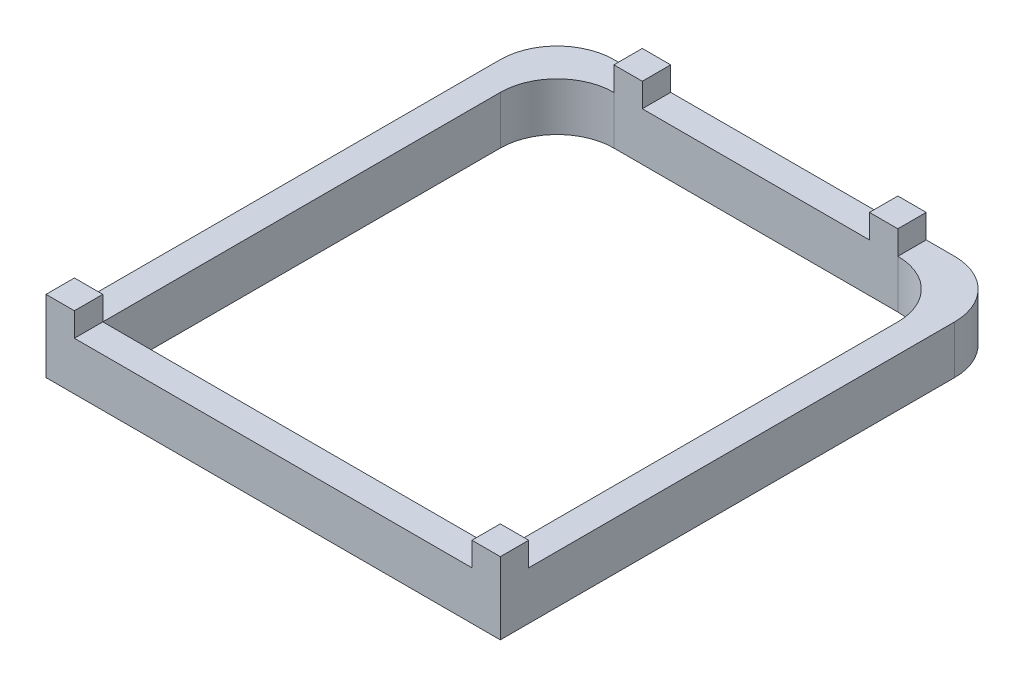
SolidWorks part; units mm, degrees
ref_plane "Front Plane" through (0, 0, 0) normal (0, 0, 1) x (1, 0, 0)
ref_plane "Top Plane" through (0, 0, 0) normal (0, 1, 0) x (1, 0, 0)
ref_plane "Right Plane" through (0, 0, 0) normal (1, 0, 0) x (0, 0, -1)
sketch "Sketch1" plane through (0, 0, 0) normal (0, 1, 0) x (1, 0, 0)
  line L1 (-5, 8) -> (5, 8)
  line L2 (-7, 6) -> (-7, -8)
  line L3 (-7, -8) -> (7, -8)
  line L4 (7, 6) -> (7, -8)
  line L5 (-7, 8) -> (7, -8) construction
  line L6 (-7, -8) -> (7, 8) construction
  arc A0 (5, 8) -> (7, 6) centre (5, 6) cw
  arc A1 (-5, 8) -> (-7, 6) centre (-5, 6) ccw
  point P0 (0, 0)
  dimension "D3" = 2
  dimension "D1" = 16
  dimension "D2" = 14
extrude "Boss-Extrude1" add sketch "Sketch1" along normal blind 1.7
sketch "Sketch2" plane through (0, 1.7, 0) normal (0, 1, 0) x (1, 0, 0)
  line L0 (-7, 6) -> (-7, -8) construction
  line L1 (-7, 2) -> (7, 2)
  line L2 (-7, 2) -> (-7, -3.5)
  line L3 (-7, -3.5) -> (7, -3.5)
  line L4 (7, 2) -> (7, -3.5)
  line L5 (7, -8) -> (7, 6) construction
  line L6 (5, 8) -> (-5, 8) construction
  line L7 (-7, -8) -> (7, -8) construction
  dimension "D1" = 6
  dimension "D2" = 4.5
extrude "Boss-Extrude2" [suppressed] add sketch "Sketch2" along normal blind 1.3
sketch "Sketch3" plane through (0, 0, 0) normal (0, 1, 0) x (1, 0, 0)
  line L0 (-7, 6) -> (-7, -8) construction
  line L1 (-6, 9) -> (6, 9)
  line L2 (-8, 7) -> (-8, -9)
  line L3 (-8, -9) -> (8, -9)
  line L4 (8, 7) -> (8, -9)
  line L5 (-8, 9) -> (8, -9) construction
  line L6 (-8, -9) -> (8, 9) construction
  line L7 (5, 8) -> (-5, 8) construction
  arc A0 (-6, 9) -> (-8, 7) centre (-6, 7) ccw
  arc A1 (6, 9) -> (8, 7) centre (6, 7) cw
  point P0 (0, 0)
  dimension "D3" = 2
  dimension "D1" = 1
  dimension "D2" = 1
extrude "Boss-Extrude3" add sketch "Sketch3" along normal blind 1.7
extrude "Cut-Extrude1" cut sketch "Sketch1<2>" along normal blind 1.7
sketch "Sketch1<2>" plane through (0, 0, 0) normal (0, 1, 0) x (1, 0, 0) same geometry as "Sketch1"
sketch "Sketch5" plane through (0, 1.7, 0) normal (0, 1, 0) x (1, 0, 0)
  line L0 (-5, 8) -> (-5, 9)
  line L1 (-7, -8) -> (-8, -8)
  line L2 (-7, -8) -> (-7, -9)
  line L3 (-7, -9) -> (-8, -9)
  line L4 (-8, -8) -> (-8, -9)
  line L5 (7, -8) -> (8, -8)
  line L6 (7, -8) -> (7, -9)
  line L7 (7, -9) -> (8, -9)
  line L8 (8, -8) -> (8, -9)
  line L9 (6, 9) -> (-6, 9) construction
  line L10 (-5, 9) -> (-4, 9)
  line L11 (-4, 9) -> (-4, 8)
  line L12 (5, 8) -> (-5, 8) construction
  line L13 (-4, 8) -> (-5, 8)
  line L14 (5, 8) -> (5, 9)
  line L15 (5, 9) -> (4, 9)
  line L16 (4, 9) -> (4, 8)
  line L17 (4, 8) -> (5, 8)
  point P27 (5, 8.5)
  dimension "D1" = 1
  dimension "D2" = 1
extrude "Boss-Extrude4" add sketch "Sketch5" along normal blind 0.84
